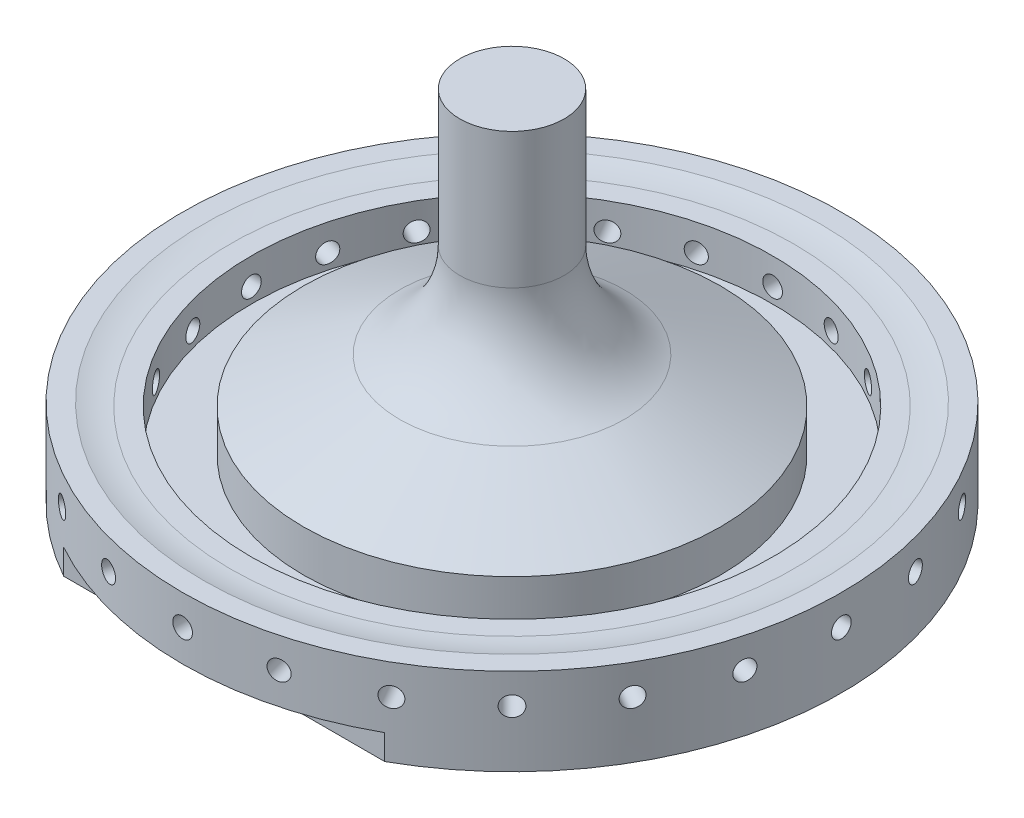
SolidWorks part; units mm, degrees
ref_plane "Front Plane" through (0, 0, 0) normal (0, 0, 1) x (1, 0, 0)
ref_plane "Top Plane" through (0, 0, 0) normal (0, 1, 0) x (1, 0, 0)
ref_plane "Right Plane" through (0, 0, 0) normal (1, 0, 0) x (0, 0, -1)
sketch "Sketch1" plane through (0, 0, 0) normal (0, 0, 1) x (1, 0, 0)
  line L0 (0, 0) -> (0, -33.5996) construction
  line L1 (0, 0) -> (3.175, 0)
  line L2 (3.175, 0) -> (3.175, -8.255)
  line L7 (20.0585, -21.822) -> (0, -21.822)
  line L8 (0, -21.822) -> (0, 0)
  line L9 (18.7885, -16.5256) -> (20.0585, -16.5256)
  line L10 (20.0585, -16.5256) -> (20.0585, -21.822)
  line L12 (18.7885, -16.5256) -> (22.6276, -15.4969) construction
  line L13 (15.875, -16.742) -> (15.875, -19.282)
  line L14 (15.875, -19.282) -> (12.7, -19.282)
  line L15 (12.7, -19.282) -> (12.7, -16.742)
  line L16 (15.875, -16.742) -> (17.145, -16.742)
  line L18 (6.8414, -14.0101) -> (12.7, -16.742)
  arc A0 (17.145, -16.742) -> (18.7885, -16.5256) centre (17.145, -10.392) ccw
  arc A1 (3.175, -8.255) -> (6.8414, -14.0101) centre (9.525, -8.255) ccw
  point P15 (12.7, -19.8398)
  point P19 (12.7, -17.5288)
  point P20 (15.3101, -17.8929)
  point P21 (15.875, -16.8299)
  point P23 (15.875, -16.742)
  point P24 (12.9797, -16.742)
  dimension "D8" = 3.175
  dimension "D2" = 6.35
  dimension "D3" = 6.35
  dimension "D4" = 8.255
  dimension "D5" = 1.27
  dimension "D6" = 15
  dimension "D7" = 65
  dimension "D9" = 1.27
  dimension "D10" = 2.54
  dimension "D12" = 2.54
  dimension "D13" = 25.4
revolve "Revolve1" add sketch "Sketch1" angle 360 about L0
ref_plane "Tangent Plane" through (0, 0, 20.0585) normal (0, 0, 1) x (1, 0, 0)
sketch "Sketch2" plane through (0, 0, 20.0585) normal (0, 0, 1) x (1, 0, 0)
  line L0 (15.875, -19.282) -> (-15.875, -19.282) construction
  line L1 (15.875, -19.282) -> (-15.875, -19.282) construction
  circle A0 centre (0, -18.3645) radius 0.6
  dimension "D1" = 1.2
  dimension "D2" = 0.635
extrude "Hole" cut sketch "Sketch2" against normal up to next
pattern_circular "Hole Pattern" count 24 over 360 about axis through (0, -16.5256, 0) along (0, 1, 0) of "Hole"
sketch "Sketch3" plane through (0, 0, 20.0585) normal (0, 0, 1) x (1, 0, 0)
  line L1 (-12.7, -20.298) -> (12.7, -20.298)
  line L2 (-12.7, -20.298) -> (-12.7, -21.822)
  line L3 (-12.7, -21.822) -> (12.7, -21.822)
  line L4 (12.7, -20.298) -> (12.7, -21.822)
  line L6 (-20.0585, -21.822) -> (20.0585, -21.822) construction
  line L7 (-20.0585, -21.822) -> (20.0585, -21.822) construction
  point P4 (0, -21.822)
  dimension "D1" = 25.4
  dimension "D2" = 1.524
extrude "Flat" cut sketch "Sketch3" against normal blind 2.54
mirror "Flats" about plane through (0, 0, 0) normal (0, 0, 1) of "Flat"
